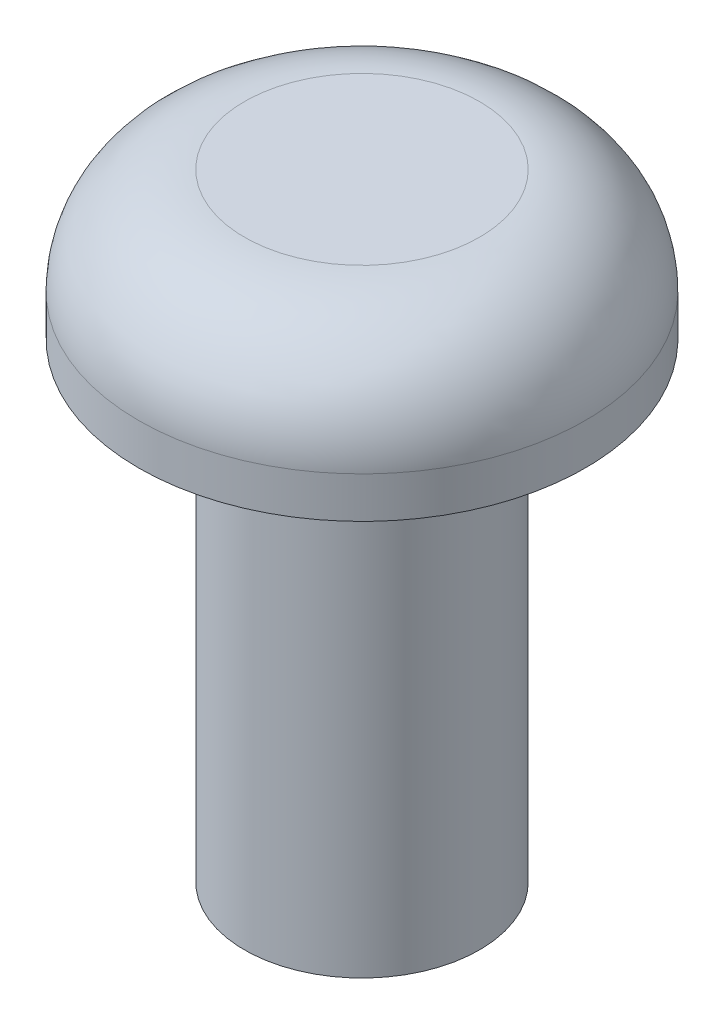
SolidWorks part; units mm, degrees
ref_plane "Front Plane" through (0, 0, 0) normal (0, 0, 1) x (1, 0, 0)
ref_plane "Top Plane" through (0, 0, 0) normal (0, 1, 0) x (1, 0, 0)
ref_plane "Right Plane" through (0, 0, 0) normal (1, 0, 0) x (0, 0, -1)
sketch "Sketch1" plane through (0, 0, 0) normal (0, 0, 1) x (1, 0, 0)
  line L0 (2, 0) -> (3.8, 0)
  line L1 (3.8, 0) -> (3.8, 0.7)
  line L2 (2, 2.5) -> (0, 2.5)
  line L3 (2, 0) -> (2, -8)
  line L4 (2, -8) -> (0, -8)
  line L5 (0, -8) -> (0, 2.5)
  arc A0 (3.8, 0.7) -> (2, 2.5) centre (2, 0.7) ccw
  dimension "D1" = 2
  dimension "D2" = 8
  dimension "D3" = 3.8
  dimension "D4" = 2.5
revolve "Revolve1" add sketch "Sketch1" angle 360 about L5
